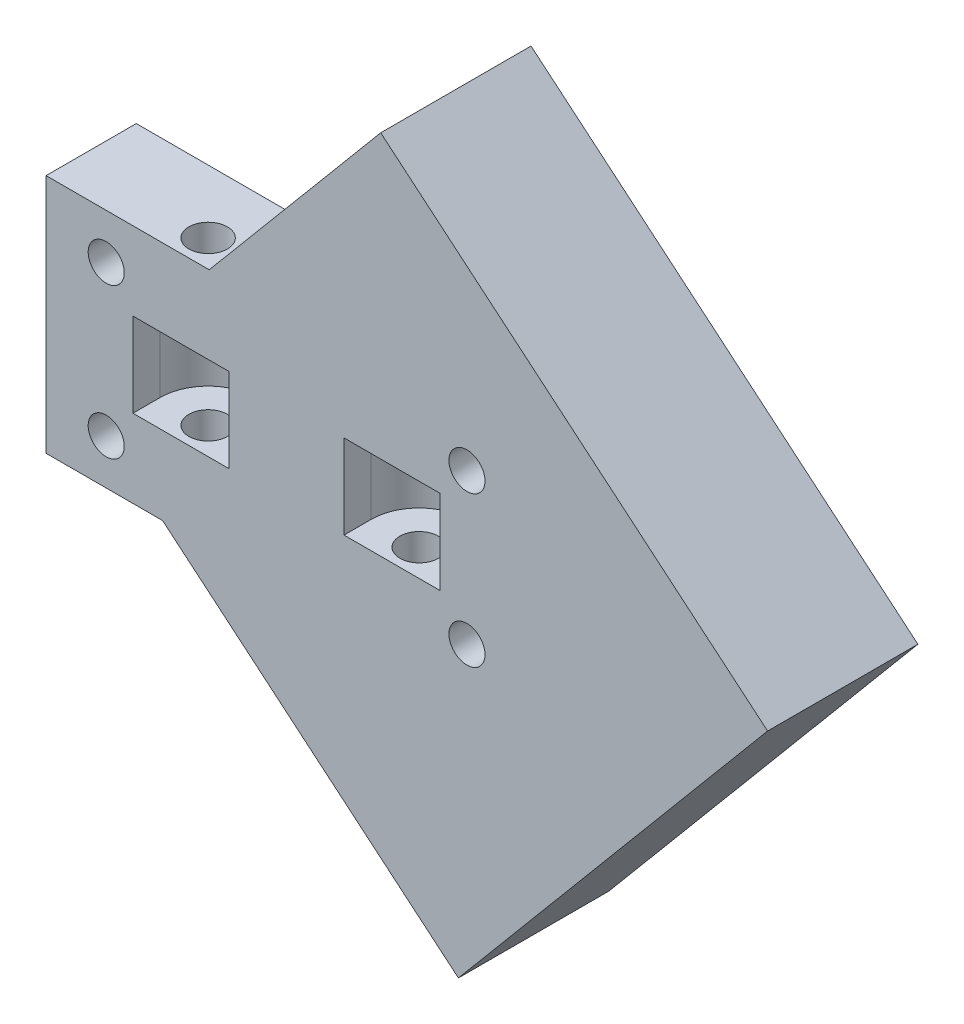
SolidWorks part; units mm, degrees
ref_plane "Front Plane" through (0, 0, 0) normal (0, 0, 1) x (1, 0, 0)
ref_plane "Top Plane" through (0, 0, 0) normal (0, 1, 0) x (1, 0, 0)
ref_plane "Right Plane" through (0, 0, 0) normal (1, 0, 0) x (0, 0, -1)
sketch "Sketch1" plane through (0, 0, 0) normal (0, 0, 1) x (1, 0, 0)
  line L2 (-38.1, -12.7) -> (-38.1, 12.7)
  line L3 (-38.1, 12.7) -> (38.1, 12.7)
  line L10 (38.1, -12.7) -> (38.1, 12.7)
  line L11 (-38.1, -12.7) -> (38.1, -12.7)
  line L14 (-38.1, 12.7) -> (38.1, -12.7) construction
  point P2 (0, 0)
  dimension "D1" = 76.2
  dimension "D2" = 25.4
extrude "Boss-Extrude1" add sketch "Sketch1" along normal blind 9.525
sketch "Sketch6" plane through (0, 0, 9.525) normal (0, 0, -1) x (-1, 0, 0)
  line L4 (-38.1, 12.7) -> (38.1, 12.7) construction
  line L6 (-38.1, -12.7) -> (-38.1, 12.7) construction
  line L7 (2.7608, 34.2863) -> (-38.1, 0)
  line L17 (35.4144, -4.6288) -> (-5.4464, -38.9151)
  line L18 (-5.4464, -38.9151) -> (-38.1, 0)
  line L22 (35.4144, -4.6288) -> (2.7608, 34.2863)
  point P0 (-38.1, 0)
  point P2 (30.55, -22.2418)
  point P8 (10.2173, 12.7)
  dimension "D1" = 53.34
  dimension "D2" = 40
  dimension "D4" = 50.8
  dimension "D8" = 50.8
extrude "Boss-Extrude2" add sketch "Sketch6" along normal blind 15.875
sketch "Sketch4" plane through (0, 0, 0) normal (0, 1, 0) x (1, 0, 0)
  line L7 (-20.8739, -9.525) -> (-38.1, -9.525) construction
  line L8 (-28.9242, -6.6675) -> (-28.9242, -9.525)
  line L9 (-18.7643, -6.6675) -> (-18.7642, -9.525)
  line L10 (-18.7642, -9.525) -> (-28.9242, -9.525)
  line L11 (-38.1, -9.525) -> (-38.1, 0) construction
  arc A2 (-18.7643, -6.6675) -> (-28.9242, -6.6675) centre (-23.8442, -6.6675) ccw
  dimension "D1" = 10.16
  dimension "D2" = 2.8575
  dimension "D3" = 14.2558
extrude "Cut-Extrude2" cut sketch "Sketch4" against normal mid plane 8.89
ref_plane "Plane3" through (-12.7, 0, 0) normal (-1, 0, 0) x (0, 0, 1)
sketch "Sketch2" plane through (0, 0, 9.525) normal (0, 0, 1) x (1, 0, 0)
  line L0 (-38.1, -12.7) -> (-25.7955, -12.7) construction
  line L1 (-38.1, 12.7) -> (-38.1, -12.7) construction
  circle A0 centre (-31.75, 7.9375) radius 1.905
  dimension "D1" = 3.81
  dimension "D2" = 20.6375
  dimension "D3" = 6.35
extrude "Cut-Extrude1" cut sketch "Sketch2" against normal up to surface (9.525 mm away) up to face at (-31.6568, -0.9258, 0)
sketch "Sketch5" plane through (0, 12.7, 0) normal (0, 1, 0) x (1, 0, 0)
  line L0 (-20.8739, -9.525) -> (-38.1, -9.525) construction
  line L1 (-38.1, -9.525) -> (-38.1, 0) construction
  circle A0 centre (-23.8442, -6.6675) radius 2.032
  dimension "D3" = 4.064
  dimension "D1" = 2.8575
  dimension "D2" = 14.2558
extrude "Cut-Extrude3" cut sketch "Sketch5" along normal blind 3.175 and the other way through all
mirror "Mirror1" about plane through (0, 0, 0) normal (0, 1, 0) of "Cut-Extrude1"
mirror "Mirror2" about plane through (-12.7, 0, 0) normal (-1, 0, 0) of "Mirror1", "Cut-Extrude3", "Cut-Extrude2"
sketch "Sketch7" plane through (0, 0, 9.525) normal (0, 0, 1) x (1, 0, 0)
  line L0 (22.9647, 12.7) -> (38.1, 0)
  line L1 (38.1, -12.7) -> (38.1, 12.7) construction
  line L2 (27.4434, -12.7) -> (38.1, 0)
  line L3 (38.1, -12.7) -> (27.4434, -12.7)
  line L4 (22.9647, 12.7) -> (38.1, 12.7)
  line L5 (38.1, 12.7) -> (38.1, 0)
  line L6 (-2.7608, 34.2863) -> (22.9647, 12.7) construction
  line L7 (27.4434, -12.7) -> (5.4464, -38.9151) construction
  line L8 (38.1, -12.7) -> (38.1, 0)
  line M7 (38.1, 12.7) -> (22.9647, 12.7)
  line M15 (27.4434, -12.7) -> (38.1, -12.7)
  line M16 (38.1, -12.7) -> (38.1, 12.7)
extrude "Cut-Extrude4" cut sketch "Sketch7" against normal through all contours L0 M7 M16 | L2 M15 M16 region at (33.0549, 8.4667, 9.525) region at (34.5478, -8.4667, 9.525)
